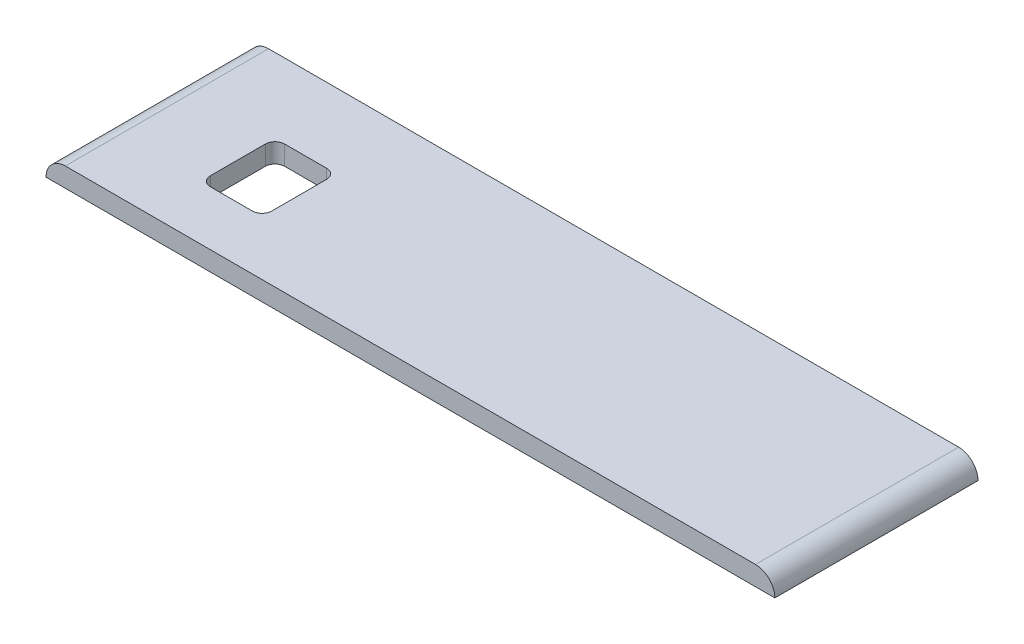
SolidWorks part; units mm, degrees
ref_plane "Спереди" through (0, 0, 0) normal (0, 0, 1) x (1, 0, 0)
ref_plane "Сверху" through (0, 0, 0) normal (0, 1, 0) x (1, 0, 0)
ref_plane "Справа" through (0, 0, 0) normal (1, 0, 0) x (0, 0, -1)
other "Configuration Table"
sketch "Эскиз1" plane through (0, 0, 0) normal (0, 1, 0) x (1, 0, 0)
  line L1 (-3, -31.5) -> (110, -31.5)
  line L2 (-3, -31.5) -> (-3, 0)
  line L3 (-3, 0) -> (110, 0)
  line L4 (110, -31.5) -> (110, 0)
  line L5 (12.55, -23.05) -> (22.05, -23.05)
  line L6 (12.55, -23.05) -> (12.55, -11.55)
  line L7 (12.55, -11.55) -> (22.05, -11.55)
  line L8 (22.05, -23.05) -> (22.05, -11.55)
extrude "Бобышка-Вытянуть1" add sketch "Эскиз1" along normal blind 3
fillet "tool_D3_R1p5_power_corners" radius 1.5 4 edges at (12.55, 1.5, 11.55) (22.05, 1.5, 11.55) (22.05, 1.5, 23.05) (12.55, 1.5, 23.05) tangent propagation no
fillet "tool_D3_R3_rear_outer_corners" radius 3 2 edges at (-3, 3, 15.75) (110, 3, 15.75)
